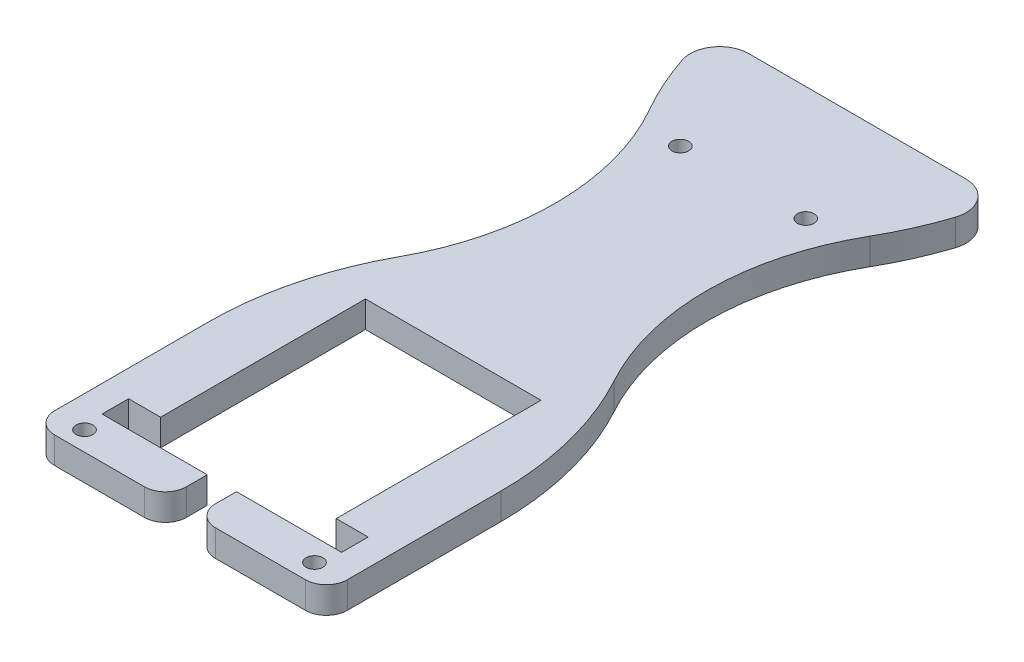
SolidWorks part; units mm, degrees
ref_plane "Front Plane" through (0, 0, 0) normal (0, 0, 1) x (1, 0, 0)
ref_plane "Top Plane" through (0, 0, 0) normal (0, 1, 0) x (1, 0, 0)
ref_plane "Right Plane" through (0, 0, 0) normal (1, 0, 0) x (0, 0, -1)
sketch "Sketch1" plane through (0, 0, 0) normal (0, 1, 0) x (1, 0, 0)
  line L0 (-35, 0) -> (-35, -200)
  line L1 (-35, -200) -> (35, -200)
  line L2 (35, -200) -> (35, 0)
  circle A0 centre (0, 0) radius 35
  point P3 (0, -200)
  dimension "D1" = 70
  dimension "D2" = 70
  dimension "D3" = 200
extrude "Boss-Extrude1" add sketch "Sketch1" along normal mid plane 6.35
sketch "Sketch2" plane through (0, 3.175, 0) normal (0, 1, 0) x (1, 0, 0)
  line L0 (35, -38) -> (-35, -38)
  line L1 (35, -200) -> (35, 0) construction
  line L2 (-35, 0) -> (-35, -200) construction
  line M1 (35, -200) -> (35, 0)
  arc M2 (35, 0) -> (-35, 0) centre (0, 0) ccw
  line M3 (-35, 0) -> (-35, -200)
  dimension "D1" = 38
extrude "Cut-Extrude1" cut sketch "Sketch2" against normal through all contours L0 M1 M2 M3
fillet "Fillet2" [suppressed] radius 8
sketch "Sketch3" plane through (0, 3.175, 0) normal (0, 1, 0) x (1, 0, 0)
  line L0 (-35, -200) -> (35, -200) construction
  line L1 (21, -190) -> (-21, -190)
  line L2 (21, -190) -> (21, -134.65)
  line L3 (21, -134.65) -> (-21, -134.65)
  line L4 (-21, -190) -> (-21, -134.65)
  line L5 (21, -190) -> (-21, -134.65) construction
  line L6 (21, -134.65) -> (-21, -190) construction
  line L7 (3.5, -200) -> (-3.5, -200)
  line L8 (3.5, -200) -> (3.5, -190)
  line L9 (3.5, -190) -> (-3.5, -190)
  line L10 (-3.5, -200) -> (-3.5, -190)
  line L11 (3.5, -200) -> (-3.5, -190) construction
  line L12 (3.5, -190) -> (-3.5, -200) construction
  line L15 (-21, -190) -> (-28.65, -190)
  line L16 (-21, -190) -> (-21, -183.65)
  line L17 (-21, -183.65) -> (-28.65, -183.65)
  line L18 (-28.65, -190) -> (-28.65, -183.65)
  line L19 (21, -190) -> (28.65, -190)
  line L20 (21, -190) -> (21, -183.65)
  line L21 (21, -183.65) -> (28.65, -183.65)
  line L22 (28.65, -190) -> (28.65, -183.65)
  point P0 (0, -162.325)
  point P5 (0, -195)
  point P14 (0, -200)
  line M12 (-35, -200) -> (35, -200)
  dimension "D1" = 10
  dimension "D2" = 7
  dimension "D3" = 55.35
  dimension "D4" = 42
  dimension "D5" = 6.35
  dimension "D6" = 7.65
extrude "Cut-Extrude2" cut sketch "Sketch3" against normal through all contours L4 L1 L2 L3 | L10 L8 L1 M12 | L18 L15 L4 L17 | L19 L22 L21 L2
fillet "Fillet3" radius 5 4 edges at (35, 0, 200) (-35, 0, 200) (3.5, 0, 200) (-3.5, 0, 200)
sketch "Sketch4" plane through (0, 3.175, 0) normal (0, 1, 0) x (1, 0, 0)
  circle A0 centre (15, -65.35) radius 2
  circle A1 centre (-15, -65.35) radius 2
  circle A2 centre (27.5, -195.35) radius 2
  circle A3 centre (-27.5, -195.35) radius 2
extrude "Cut-Extrude3" cut sketch "Sketch4" against normal through all
sketch "Sketch5" plane through (0, 3.175, 0) normal (0, 1, 0) x (1, 0, 0)
  line L1 (-35, -134.65) -> (-35, -49.65)
  line L2 (-35, -38) -> (-35, -195) construction
  arc A0 (-35, -134.65) -> (-35, -49.65) centre (-80, -92.15) ccw
  point P3 (0, 0)
  point P4 (22.84, -57.9199)
  point P7 (0, 0)
  dimension "D2" = 45
  dimension "D1" = 85
extrude "Cut-Extrude4" cut sketch "Sketch5" against normal through all
mirror "Mirror1" about plane through (0, 0, 0) normal (1, 0, 0) of "Cut-Extrude4"
fillet "Fillet4" radius 76 4 edges at (35, 0, 134.65) (35, 0, 49.65) (-35, 0, 49.65) (-35, 0, 134.65)
fillet "Fillet5" radius 7 2 edges at (35, 0, 38) (-35, 0, 38)
